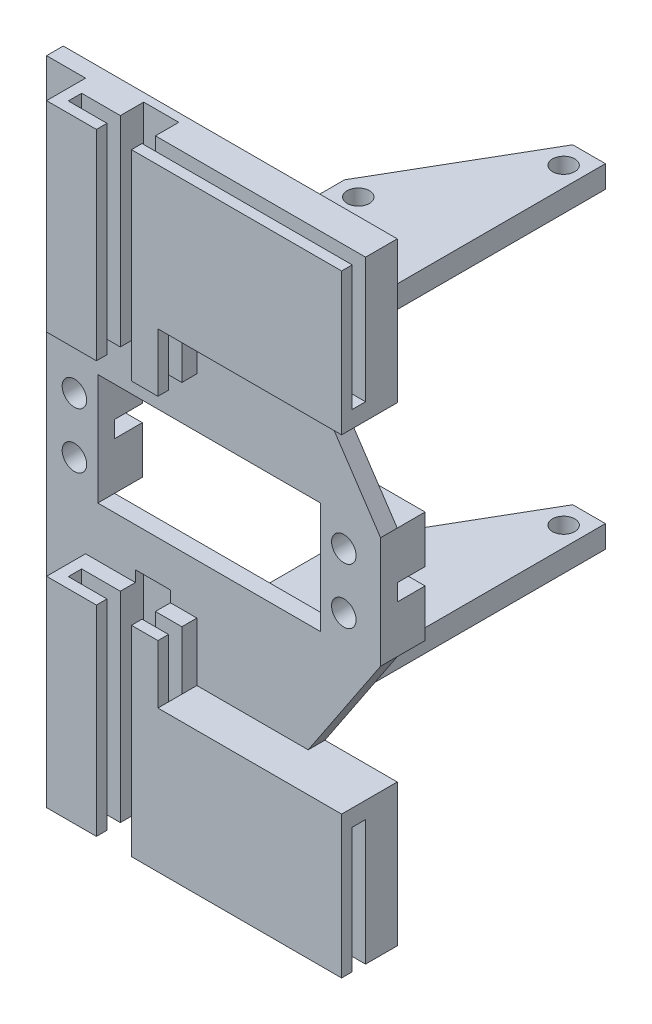
SolidWorks part; units mm, degrees
ref_plane "前视基准面" through (0, 0, 0) normal (0, 0, 1) x (1, 0, 0)
ref_plane "上视基准面" through (0, 0, 0) normal (0, 1, 0) x (1, 0, 0)
ref_plane "右视基准面" through (0, 0, 0) normal (1, 0, 0) x (0, 0, -1)
sketch "草图1" plane through (0, 0, 0) normal (0, 0, 1) x (1, 0, 0)
  line L0 (0, -55) -> (0, 55) construction
  line L1 (23, 10) -> (49.2, 10)
  line L2 (15.95, 19) -> (7, 19)
  line L3 (0, 40) -> (24.25, 40)
  line L4 (0, 40) -> (0, -40)
  line L5 (0, -40) -> (24.25, -40)
  line L6 (60, 10) -> (60, -10)
  line L7 (9.2, 10) -> (16, 10)
  line L8 (9.2, 10) -> (9.2, -10)
  line L9 (9.2, -10) -> (16, -10)
  line L10 (49.2, 10) -> (49.2, -10)
  line L11 (16.15, 40) -> (22.25, 40)
  line L12 (15.95, 38) -> (15.95, 19)
  line L14 (22.25, 38) -> (22.25, 19)
  line L15 (7, 19) -> (7, 40)
  line L16 (7, 40) -> (16.15, 40)
  line L17 (22.25, 19) -> (24.25, 19)
  line L18 (24.25, 19) -> (24.25, 40)
  line L19 (24.25, 40) -> (22.25, 40)
  line L20 (15.95, 38) -> (22.25, 38)
  line L21 (55, 0) -> (-55, 0) construction
  line L22 (7, -40) -> (16.15, -40)
  line L23 (7, -19) -> (7, -40)
  line L24 (15.95, -19) -> (7, -19)
  line L25 (15.95, -38) -> (15.95, -19)
  line L26 (15.95, -38) -> (22.25, -38)
  line L27 (22.25, -38) -> (22.25, -19)
  line L28 (22.25, -19) -> (24.25, -19)
  line L29 (24.25, -19) -> (24.25, -40)
  line L30 (24.25, -40) -> (22.25, -40)
  line L31 (16.15, -40) -> (22.25, -40)
  line L32 (24.25, 19) -> (27, 19)
  line L40 (23, -10) -> (49.2, -10)
  line L41 (27, 29.5) -> (40, 29.5)
  line L42 (40, 29.5) -> (40, 40)
  line L43 (60, 10) -> (40, 40)
  line L44 (27, -29.5) -> (40, -29.5)
  line L45 (40, -29.5) -> (40, -40)
  line L46 (40, 40) -> (40, 45)
  line L47 (40, 45) -> (24.25, 45)
  line L48 (24.25, 45) -> (24.25, 40)
  line L49 (16, -10) -> (23, -10)
  line L50 (40, -40) -> (40, -45)
  line L51 (40, -45) -> (24.25, -45)
  line L52 (24.25, -45) -> (24.25, -40)
  line L53 (16, 10) -> (23, 10)
  line L54 (60, -10) -> (40, -40)
  line L55 (27, 19) -> (27, 29.5)
  line L56 (24.25, -19) -> (27, -19)
  line L57 (27, -19) -> (27, -29.5)
  circle A0 centre (5, 5) radius 2.2
  circle A1 centre (5, -5) radius 2.2
  circle A2 centre (53.4, 5) radius 2.2
  circle A3 centre (53.4, -5) radius 2.2
  dimension "D2" = 2
extrude "凸台-拉伸1" add sketch "草图1" along normal mid plane 3 contours L28 L29 L5 L6 L3 L18 L17 L14 L20 L12 L2 L15 L4 L23 L24 L25 L26 L27 A3 A2 A1 A0 L7 L10 L9 L8 region at (16.95, 28.5, 0)
extrude "凸台-拉伸2" add sketch "草图1<3>" along normal blind 10 from surface contours L12 L20 L14 L17 L18 L3 L15 L2 | L29 L28 L27 L26 L25 L24 L23 L5 region at (13.9101, 29.9935, 0) region at (13.9101, -29.9935, 0) starting at face at (55.6, -5, -1.5)
sketch "草图1<3>" plane through (0, 0, 0) normal (0, 0, 1) x (1, 0, 0) same geometry as "草图1"
sketch "草图2" plane through (0, -40, 0) normal (0, -1, 0) x (1, 0, 0)
  line L1 (15.95, 8.5) -> (22.25, 8.5)
  line L2 (15.95, 8.5) -> (15.95, 1.5)
  line L3 (15.95, 1.5) -> (22.25, 1.5)
  line L4 (22.25, 8.5) -> (22.25, 1.5)
extrude "切除-拉伸1" cut sketch "草图2" against normal blind 80
sketch "草图3" plane through (7, 0, 0) normal (-1, 0, 0) x (0, 0, 1)
  line L1 (4.2, -38) -> (6.6, -38)
  line L2 (4.2, -38) -> (4.2, -19)
  line L3 (4.2, -19) -> (6.6, -19)
  line L4 (6.6, -38) -> (6.6, -19)
  line L5 (8.5, -19) -> (1.5, -19) construction
  line L6 (5.5, 0) -> (-5.5, 0) construction
  line L7 (4.2, 19) -> (6.6, 19)
  line L8 (6.6, 38) -> (6.6, 19)
  line L9 (4.2, 38) -> (6.6, 38)
  line L10 (4.2, 38) -> (4.2, 19)
extrude "切除-拉伸2" cut sketch "草图3" against normal blind 80 from offset 2 offset against normal yes
extrude "凸台-拉伸3" add sketch "草图1<4>" along normal blind 10 from surface contours L41 L42 L3 L18 | L45 L44 L29 L5 region at (31.4375, 35.875, 0) region at (31.4375, -35.875, 0) starting at face at (30.3125, 0, -1.5)
sketch "草图1<4>" plane through (0, 0, 0) normal (0, 0, 1) x (1, 0, 0) same geometry as "草图1"
sketch "草图4" plane through (0, -45, 0) normal (0, -1, 0) x (1, 0, 0)
  line L1 (22.25, 6.6) -> (40, 6.6)
  line L2 (22.25, 6.6) -> (22.25, 4.2)
  line L3 (22.25, 4.2) -> (40, 4.2)
  line L4 (40, 6.6) -> (40, 4.2)
extrude "切除-拉伸3" cut sketch "草图4" against normal blind 12.5
extrude "切除-拉伸4" cut sketch "草图4<2>" along normal blind 12.5 from surface starting at face at (32.125, 45, 3.5)
sketch "草图4<2>" plane through (0, -45, 0) normal (0, -1, 0) x (1, 0, 0) same geometry as "草图4"
sketch "草图6" plane through (0, 45, 0) normal (0, 1, 0) x (1, 0, 0)
  line L0 (21.0788, 1.5) -> (42, 1.5)
  line L1 (21.0788, 1.5) -> (21.0788, 30.938)
  line L3 (42, 7.5) -> (42, 1.5)
  line L8 (42, 7.5) -> (42, 56.8941)
  line L9 (21.0788, 30.938) -> (36.1295, 56.8941)
  line L10 (36.1295, 56.8941) -> (42, 56.8941)
  circle A0 centre (25, 29.5) radius 2
  circle A1 centre (38.5, 52.8827) radius 2
extrude "凸台-拉伸4" add sketch "草图6" against normal blind 4 from offset 15 offset against normal yes
extrude "凸台-拉伸5" add sketch "草图6<2>" along normal blind 4 from offset 75 offset against normal yes
sketch "草图6<2>" plane through (0, 45, 0) normal (0, 1, 0) x (1, 0, 0) same geometry as "草图6"
sketch "草图7" plane through (0, 19, 0) normal (0, -1, 0) x (1, 0, 0)
  line L1 (9, 6.6) -> (15.95, 6.6)
  line L2 (9, 6.6) -> (9, 4.2)
  line L3 (9, 4.2) -> (15.95, 4.2)
  line L4 (15.95, 6.6) -> (15.95, 4.2)
extrude "切除-拉伸5" cut sketch "草图7" against normal blind 90 from offset 60
sketch "草图9" plane through (0, 40, 0) normal (0, 1, 0) x (1, 0, 0)
  line L1 (22.25, -1.5) -> (15.95, -1.5)
  line L2 (22.25, -1.5) -> (22.25, 0)
  line L3 (22.25, 0) -> (15.95, 0)
  line L4 (15.95, -1.5) -> (15.95, 0)
extrude "切除-拉伸7" cut sketch "草图9" against normal blind 23
sketch "草图10" plane through (0, -40, 0) normal (0, -1, 0) x (1, 0, 0)
  line L1 (22.25, 1.5) -> (15.95, 1.5)
  line L2 (22.25, 1.5) -> (22.25, 0)
  line L3 (22.25, 0) -> (15.95, 0)
  line L4 (15.95, 1.5) -> (15.95, 0)
extrude "切除-拉伸8" cut sketch "草图10" against normal blind 23
sketch "草图11" plane through (0, 19, 0) normal (0, -1, 0) x (1, 0, 0)
  line L1 (24.25, 6.6) -> (27, 6.6)
  line L2 (24.25, 6.6) -> (24.25, 4.2)
  line L3 (24.25, 4.2) -> (27, 4.2)
  line L4 (27, 6.6) -> (27, 4.2)
extrude "切除-拉伸9" cut sketch "草图11" against normal blind 30 and the other way blind 70
sketch "草图12" plane through (40, 0, 0) normal (1, 0, 0) x (0, 0, -1)
  line L0 (-8.5, -45) -> (-8.5, -29.5)
  line L1 (-8.5, -29.5) -> (-8.5, -45) construction
  line L2 (-8.5, -45) -> (-6.6, -45) construction
  line L3 (-8.5, -29.5) -> (1.5, -29.5)
  line L4 (1.5, -10) -> (1.5, -40) construction
  line L5 (1.5, -29.5) -> (1.5, -45)
  line L6 (1.5, -45) -> (-4.2, -45)
  line L7 (-4.2, -45) -> (-4.2, -32.5)
  line L8 (-4.2, -32.5) -> (-6.6, -32.5)
  line L9 (-6.6, -32.5) -> (-6.6, -45)
  line L10 (-6.6, -45) -> (-8.5, -45)
extrude "凸台-拉伸6" add sketch "草图12" along normal blind 20
sketch "草图13" plane through (40, 0, 0) normal (1, 0, 0) x (0, 0, -1)
  line L0 (-8.5, 45) -> (-8.5, 29.5)
  line L1 (-8.5, 29.5) -> (1.5, 29.5)
  line L2 (1.5, 26) -> (1.5, 30) construction
  line L3 (1.5, 29.5) -> (1.5, 45)
  line L4 (1.5, 45) -> (-4.2, 45)
  line L5 (-4.2, 45) -> (-4.2, 32.5)
  line L6 (-4.2, 32.5) -> (-6.6, 32.5)
  line L7 (-6.6, 32.5) -> (-6.6, 45)
  line L8 (-6.6, 45) -> (-8.5, 45)
extrude "凸台-拉伸7" add sketch "草图13" along normal blind 20
sketch "草图15" plane through (0, 40, 0) normal (0, 1, 0) x (1, 0, 0)
  line L0 (0, -1.5) -> (7, -1.5)
  line L1 (0, -35.9667) -> (0, 35.9667) construction
  line L2 (0, -1.5) -> (7, -1.5) construction
  line L3 (7, -1.5) -> (7, -8.5)
  line L4 (7, -8.5) -> (15.95, -8.5)
  line L5 (15.95, -8.5) -> (15.95, -6.6)
  line L6 (15.95, -6.6) -> (9, -6.6)
  line L7 (9, -6.6) -> (9, -4.2)
  line L8 (9, -4.2) -> (15.95, -4.2)
  line L9 (15.95, -4.2) -> (15.95, 0)
  line L10 (-33, 0) -> (33, 0) construction
  line L12 (15.95, 0) -> (22.25, 0)
  line L13 (22.25, -1.5) -> (22.25, 0) construction
  line L14 (22.25, 0) -> (22.25, -4.2)
  line L15 (22.25, -4.2) -> (60, -4.2)
  line L16 (60, -4.2) -> (60, 1.5)
  line L17 (60, 1.5) -> (0, 1.5)
  line L18 (0, 1.5) -> (0, -1.5)
  line L19 (22.25, -6.6) -> (22.25, -8.5)
  line L20 (22.25, -6.6) -> (22.25, -8.5) construction
  line L21 (22.25, -8.5) -> (24.25, -8.5) construction
  line L22 (22.25, -8.5) -> (60, -8.5)
  line L23 (60, -8.5) -> (60, -6.6)
  line L24 (60, -6.6) -> (22.25, -6.6)
extrude "凸台-拉伸8" add sketch "草图15" along normal blind 15
sketch "草图16" plane through (0, -40, 0) normal (0, -1, 0) x (1, 0, 0)
  line L0 (15.95, 8.5) -> (7, 8.5)
  line L1 (7, 8.5) -> (7, 1.5)
  line L2 (7, 1.5) -> (0, 1.5)
  line L3 (0, 1.5) -> (0, -1.5)
  line L4 (0, -1.5) -> (60, -1.5)
  line L5 (60, -1.5) -> (60, 4.2)
  line L6 (60, 4.2) -> (22.25, 4.2)
  line L7 (22.25, 4.2) -> (22.25, 0)
  line L8 (33, 0) -> (-33, 0) construction
  line L9 (22.25, 0) -> (22.25, 1.5) construction
  line L10 (22.25, 0) -> (15.95, 0)
  line L11 (15.95, 0) -> (15.95, 4.2)
  line L12 (15.95, 4.2) -> (9, 4.2)
  line L13 (9, 4.2) -> (9, 6.6)
  line L14 (9, 6.6) -> (15.95, 6.6)
  line L15 (15.95, 6.6) -> (15.95, 8.5)
  line L16 (22.25, 8.5) -> (22.25, 6.6)
  line L17 (22.25, 6.6) -> (60, 6.6)
  line L18 (60, 6.6) -> (60, 8.5)
  line L19 (60, 8.5) -> (22.25, 8.5)
extrude "凸台-拉伸9" add sketch "草图16" along normal blind 15
sketch "草图17" plane through (0, 0, -1.5) normal (0, 0, -1) x (-1, 0, 0)
  line L0 (-49.2, -10) -> (-60, -10)
  line L1 (-60, -10) -> (-60, -1.5)
  line L2 (-60, 10) -> (-60, -10) construction
  line L3 (-60, 10) -> (-47, 29.5) construction
  line L4 (-60, 10) -> (-49.2, 10)
  line L5 (-49.2, 10) -> (-49.2, 1.5)
  line L6 (-9.2, -10) -> (0, -10)
  line L7 (0, 55) -> (0, -55) construction
  line L8 (0, -10) -> (0, -1.5)
  line L9 (0, 10) -> (-9.2, 10)
  line L10 (-60, 1.5) -> (-49.2, 1.5)
  line L11 (-9.2, 10) -> (-9.2, 1.5)
  line L13 (-49.2, -1.5) -> (-60, -1.5)
  line L15 (-9.2, 1.5) -> (0, 1.5)
  line L17 (0, -1.5) -> (-9.2, -1.5)
  line L19 (-9.2, -1.5) -> (-9.2, -10)
  line L20 (0, 1.5) -> (0, 10)
  line L21 (-49.2, -1.5) -> (-49.2, -10)
  line L22 (-60, 1.5) -> (-60, 10)
  circle A0 centre (-5, -5) radius 2.2
  circle A1 centre (-5, 5) radius 2.2
  circle A2 centre (-53.4, -5) radius 2.2
  circle A3 centre (-53.4, 5) radius 2.2
  point P39 (-49.2, 0)
extrude "凸台-拉伸10" add sketch "草图17" along normal blind 5
